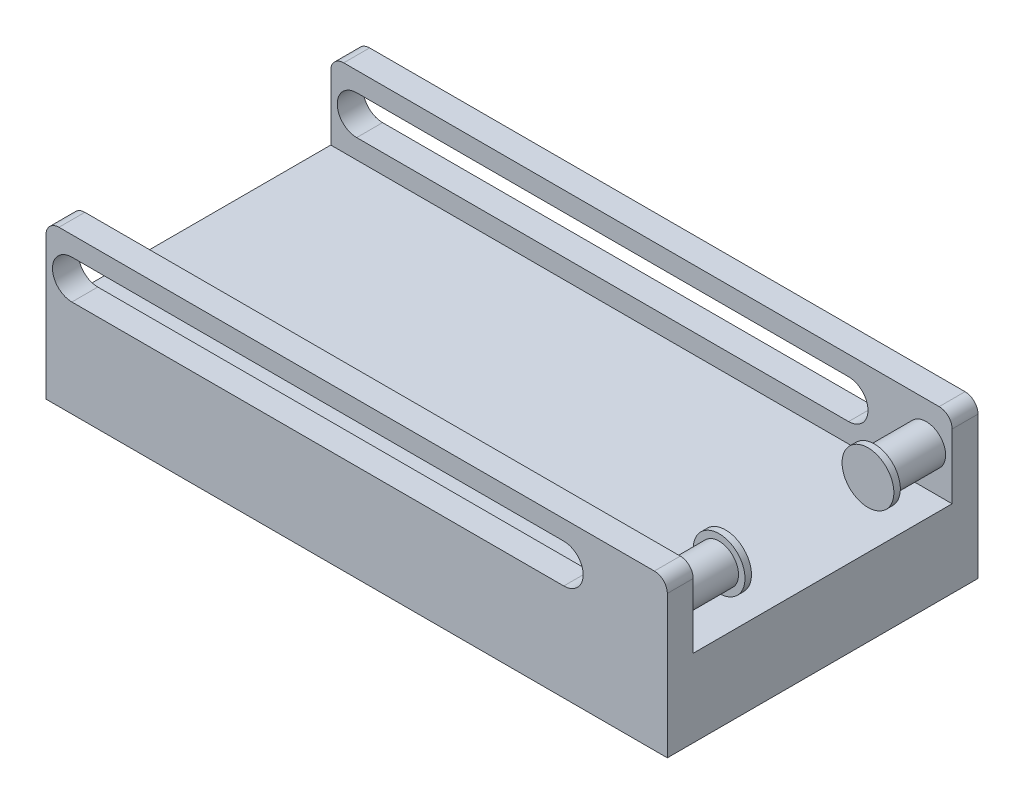
SolidWorks part; units mm, degrees
ref_plane "Front Plane" through (0, 0, 0) normal (0, 0, 1) x (1, 0, 0)
ref_plane "Top Plane" through (0, 0, 0) normal (0, 1, 0) x (1, 0, 0)
ref_plane "Right Plane" through (0, 0, 0) normal (1, 0, 0) x (0, 0, -1)
sketch "Sketch1" plane through (0, 0, 0) normal (0, 1, 0) x (1, 0, 0)
  line L1 (0, 0) -> (609.6, 0)
  line L2 (0, 0) -> (0, 304.8)
  line L3 (0, 304.8) -> (609.6, 304.8)
  line L4 (609.6, 0) -> (609.6, 304.8)
  dimension "D1" = 609.6
  dimension "D2" = 304.8
extrude "Boss-Extrude1" add sketch "Sketch1" along normal blind 76.2
sketch "Sketch2" plane through (0, 76.2, 0) normal (0, 1, 0) x (1, 0, 0)
  line L1 (0, 0) -> (533.4, 0)
  line L2 (0, 0) -> (0, 25.4)
  line L3 (0, 25.4) -> (533.4, 25.4)
  line L5 (533.4, 25.4) -> (533.4, 0)
  line L6 (609.6, 0) -> (609.6, 304.8) construction
  dimension "D1" = 76.2
extrude "Boss-Extrude2" add sketch "Sketch2" along normal blind 76.2
sketch "Sketch3" plane through (0, 0, -25.4) normal (0, 0, -1) x (-1, 0, 0)
  line L0 (-533.4, 152.4) -> (-533.4, 76.2) construction
  line L1 (0, 152.4) -> (0, 76.2) construction
  line L2 (-533.4, 114.3) -> (-508, 114.3) construction
  line L3 (0, 114.3) -> (-25.4, 114.3) construction
  line L4 (-508, 114.3) -> (-25.4, 114.3) construction
  line L5 (-508, 133.35) -> (-25.4, 133.35)
  line L6 (-508, 95.25) -> (-25.4, 95.25)
  arc A0 (-508, 133.35) -> (-508, 95.25) centre (-508, 114.3) ccw
  arc A1 (-25.4, 95.25) -> (-25.4, 133.35) centre (-25.4, 114.3) ccw
  point P12 (-266.7, 114.3)
  dimension "D1" = 25.4
  dimension "D2" = 25.4
  dimension "D3" = 38.1
extrude "Cut-Extrude1" cut sketch "Sketch3" against normal through all
ref_plane "Plane1" through (0, 0, -152.4) normal (0, 0, 1) x (1, 0, 0)
sketch "Sketch4" plane through (533.4, 0, 0) normal (1, 0, 0) x (0, 0, -1)
  line L1 (0, 152.4) -> (25.4, 152.4)
  line L2 (0, 152.4) -> (0, 76.2)
  line L3 (0, 76.2) -> (25.4, 76.2)
  line L4 (25.4, 152.4) -> (25.4, 76.2)
extrude "Boss-Extrude3" add sketch "Sketch4" along normal through all
sketch "Sketch5" plane through (0, 0, -25.4) normal (0, 0, 1) x (1, 0, 0)
  line L1 (0, 152.4) -> (609.6, 152.4) construction
  line L2 (609.6, 152.4) -> (609.6, 0) construction
  circle A0 centre (584.2, 114.3) radius 19.05
  dimension "D1" = 38.1
  dimension "D2" = 25.4
extrude "Boss-Extrude4" add sketch "Sketch5" against normal blind 50.8 contours A0
sketch "Sketch6" plane through (0, 0, -76.2) normal (0, 0, -1) x (-1, 0, 0)
  circle A0 centre (-584.2, 114.3) radius 25.4
extrude "Boss-Extrude7" add sketch "Sketch6" along normal blind 6.35
fillet "Fillet1" radius 12.7 2 edges at (0, 152.4, -12.7) (609.6, 152.4, -12.7) tangent propagation no
mirror "Mirror1" about plane through (0, 0, -152.4) normal (0, 0, 1) of "Boss-Extrude7", "Boss-Extrude3", "Boss-Extrude4", "Fillet1", "Boss-Extrude2", "Cut-Extrude1"
